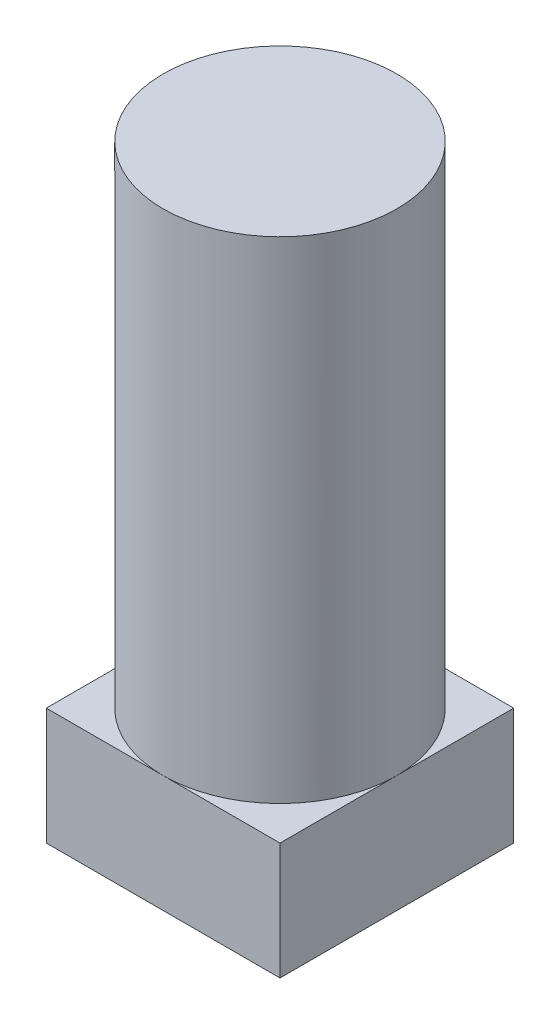
SolidWorks part; units mm, degrees
ref_plane "Front Plane" through (0, 0, 0) normal (0, 0, 1) x (1, 0, 0)
ref_plane "Top Plane" through (0, 0, 0) normal (0, 1, 0) x (1, 0, 0)
ref_plane "Right Plane" through (0, 0, 0) normal (1, 0, 0) x (0, 0, -1)
sketch "Sketch1" plane through (0, 0, 0) normal (0, 1, 0) x (1, 0, 0)
  line L1 (-2.5, -2.5) -> (2.5, -2.5)
  line L2 (-2.5, -2.5) -> (-2.5, 2.5)
  line L3 (-2.5, 2.5) -> (2.5, 2.5)
  line L4 (2.5, -2.5) -> (2.5, 2.5)
  line L5 (-2.5, -2.5) -> (2.5, 2.5) construction
  line L6 (-2.5, 2.5) -> (2.5, -2.5) construction
  point P0 (0, 0)
  dimension "D1" = 5
extrude "Boss-Extrude1" add sketch "Sketch1" along normal blind 2.5 contours L2 L3 L4 L1
sketch "Sketch2" plane through (0, 2.5, 0) normal (0, 1, 0) x (1, 0, 0)
  line L0 (2.5, -2.5) -> (2.5, 2.5) construction
  circle A0 centre (0, 0) radius 2.5
extrude "Boss-Extrude2" add sketch "Sketch2" along normal blind 10.5
equation "\"a\"= 1"
equation "\"b\"= 1"
equation "\"c\"= 1"
equation "\"d\"= 1"
equation "\"e\"= 1"
equation "\"x\"= 1"
equation "\"y\"= 1"
equation "\"z\"= 1"
